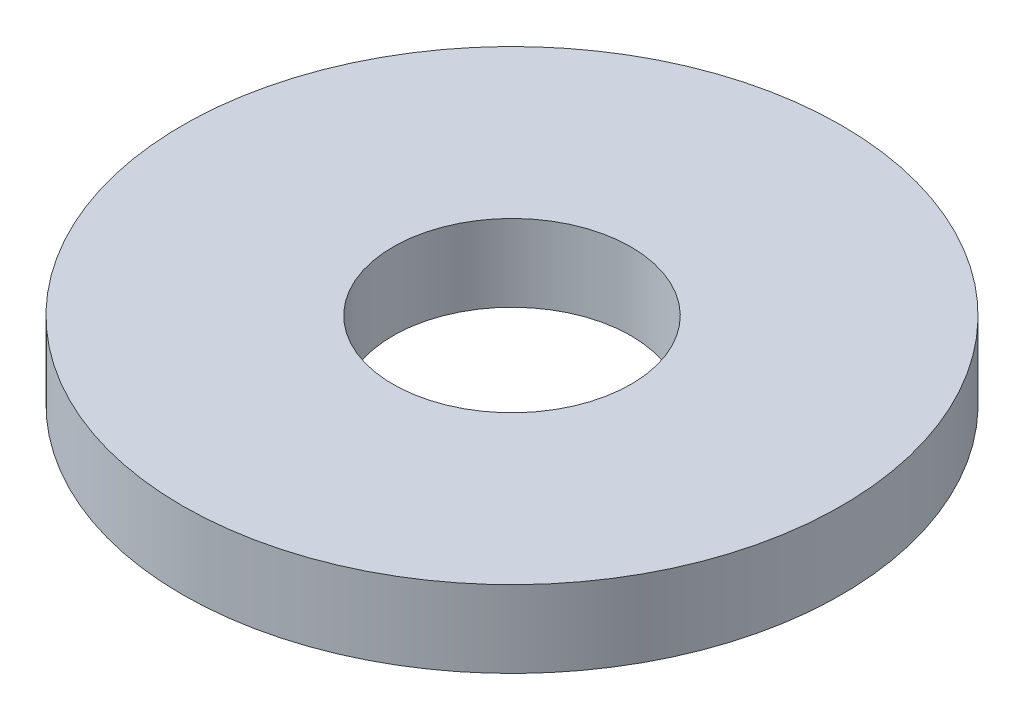
SolidWorks part; units mm, degrees
ref_plane "Front Plane" through (0, 0, 0) normal (0, 0, 1) x (1, 0, 0)
ref_plane "Top Plane" through (0, 0, 0) normal (0, 1, 0) x (1, 0, 0)
ref_plane "Right Plane" through (0, 0, 0) normal (1, 0, 0) x (0, 0, -1)
sketch "Sketch1" plane through (0, 0, 0) normal (0, 1, 0) x (1, 0, 0)
  circle A0 centre (0, 0) radius 90
  dimension "FLANGE_OD" = 180
extrude "Boss-Extrude1" add sketch "Sketch1" along normal blind 21
sketch "Sketch2" plane through (0, 0, 0) normal (0, 1, 0) x (1, 0, 0)
  circle A0 centre (0, 0) radius 32.5
  dimension "BORE_D" = 65
extrude "Cut-Extrude1" cut sketch "Sketch2" along normal through all
sketch "Sketch3" plane through (0, 21, 0) normal (0, 1, 0) x (1, 0, 0)
  circle A0 centre (0, 0) radius 26.621 construction
  circle A1 centre (-26.621, 0) radius 1.6281
  dimension "BOLT_D" = 3.2563
  dimension "BOLT_PCD" = 53.242
extrude "Cut-Extrude2" cut sketch "Sketch3" against normal blind 16.7231 rebuild error yes
pattern_circular "CirPattern1" count 3 over 360 rebuild error yes
